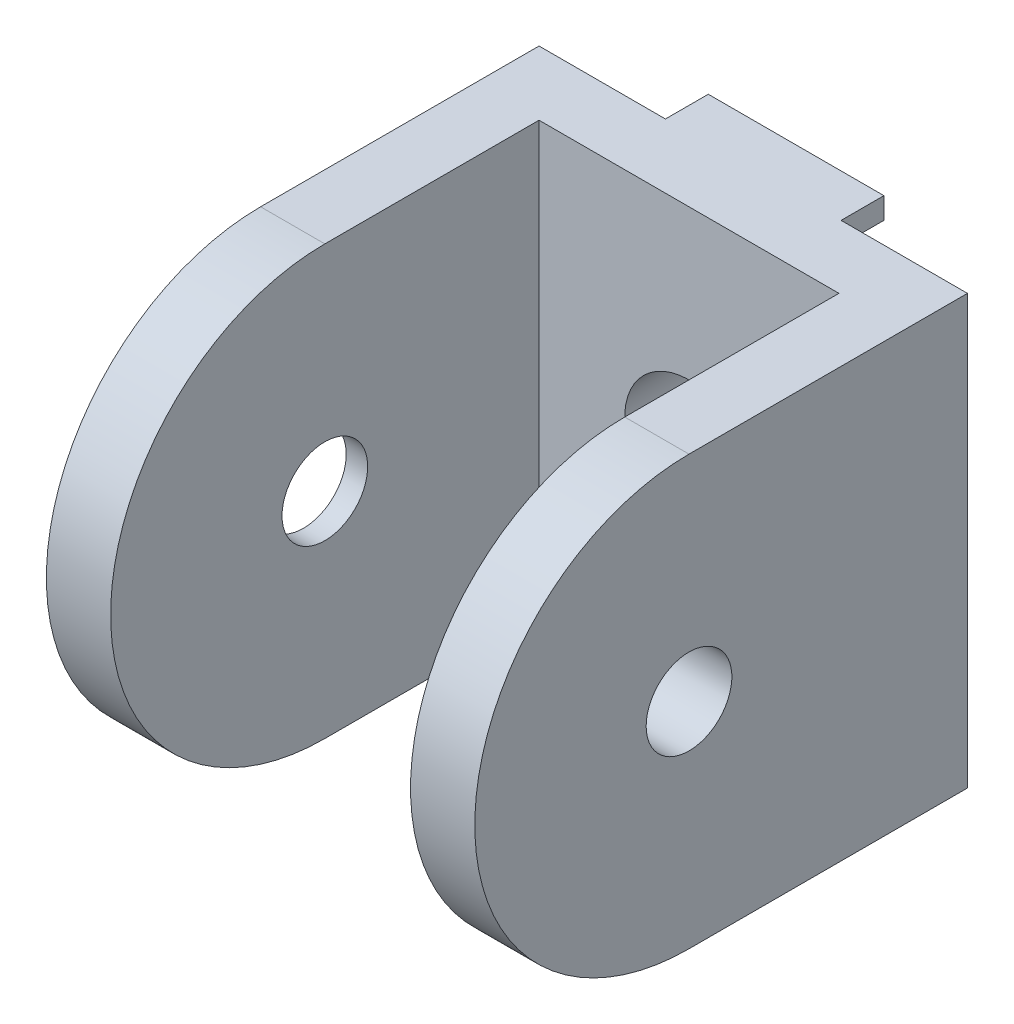
SolidWorks part; units mm, degrees
ref_plane "前视基准面" through (0, 0, 0) normal (0, 0, 1) x (1, 0, 0)
ref_plane "上视基准面" through (0, 0, 0) normal (0, 1, 0) x (1, 0, 0)
ref_plane "右视基准面" through (0, 0, 0) normal (1, 0, 0) x (0, 0, -1)
sketch "草图1" plane through (0, 0, 0) normal (0, 0, 1) x (1, 0, 0)
  line L1 (-10, -10) -> (10, -10)
  line L2 (-10, -10) -> (-10, 10)
  line L3 (-10, 10) -> (10, 10)
  line L4 (10, -10) -> (10, 10)
  line L5 (-10, -10) -> (10, 10) construction
  line L6 (-10, 10) -> (10, -10) construction
  point P0 (0, 0)
  dimension "D1" = 20
  dimension "D2" = 20
extrude "凸台-拉伸1" add sketch "草图1" along normal blind 3
sketch "草图2" plane through (0, 0, 3) normal (0, 0, 1) x (1, 0, 0)
  line L0 (10, 10) -> (-10, 10) construction
  line L1 (-10, -10) -> (-7, -10)
  line L2 (-10, -10) -> (-10, 10)
  line L3 (-10, 10) -> (-7, 10)
  line L4 (-7, -10) -> (-7, 10)
  line L5 (0, 0) -> (0, 12.8397) construction
  line L6 (10, -10) -> (7, -10)
  line L7 (10, -10) -> (10, 10)
  line L8 (7, -10) -> (7, 10)
  line L9 (10, 10) -> (7, 10)
  dimension "D1" = 3
extrude "凸台-拉伸2" add sketch "草图2" along normal blind 20
sketch "草图3" plane through (-10, 0, 0) normal (-1, 0, 0) x (0, 0, 1)
  line L0 (23, 10) -> (23, -10) construction
  line L1 (23, 10) -> (0, 10) construction
  line L2 (13, -10) -> (13, 10) construction
  arc A0 (13, -10) -> (13, 10) centre (13, 0) ccw
  dimension "D1" = 20
extrude "切除-拉伸2" cut sketch "草图3" against normal through all and the other way through all flip side to cut
sketch "草图4" plane through (-10, 0, 0) normal (-1, 0, 0) x (0, 0, 1)
  circle A0 centre (13, 0) radius 2
  dimension "D1" = 4
extrude "切除-拉伸3" cut sketch "草图4" against normal through all
sketch "草图5" plane through (-10, 0, 0) normal (-1, 0, 0) x (0, 0, 1)
  circle A0 centre (13, 0) radius 5
  dimension "D1" = 10
extrude "切除-拉伸4" cut sketch "草图5" against normal blind 2
sketch "草图6" plane through (0, 0, 3) normal (0, 0, 1) x (1, 0, 0)
  circle A0 centre (0, 0) radius 3
  dimension "D1" = 6
extrude "切除-拉伸5" cut sketch "草图6" against normal through all
sketch "草图7" plane through (0, 0, 0) normal (0, 0, -1) x (-1, 0, 0)
  line L0 (-10, 10) -> (10, 10) construction
  line L1 (-4.1, 10) -> (4.1, 10)
  line L2 (-4.1, 10) -> (-4.1, 9)
  line L3 (-4.1, 9) -> (4.1, 9)
  line L4 (4.1, 10) -> (4.1, 9)
  line L5 (0, 0) -> (-9.0525, 0) construction
  line L6 (4.1, -10) -> (4.1, -9)
  line L7 (-4.1, -10) -> (-4.1, -9)
  line L8 (-4.1, -9) -> (4.1, -9)
  line L9 (-4.1, -10) -> (4.1, -10)
  point P9 (0, 10)
  point P10 (0, 10)
  dimension "D1" = 8.2
  dimension "D2" = 1
extrude "凸台-拉伸3" add sketch "草图7" along normal blind 2
